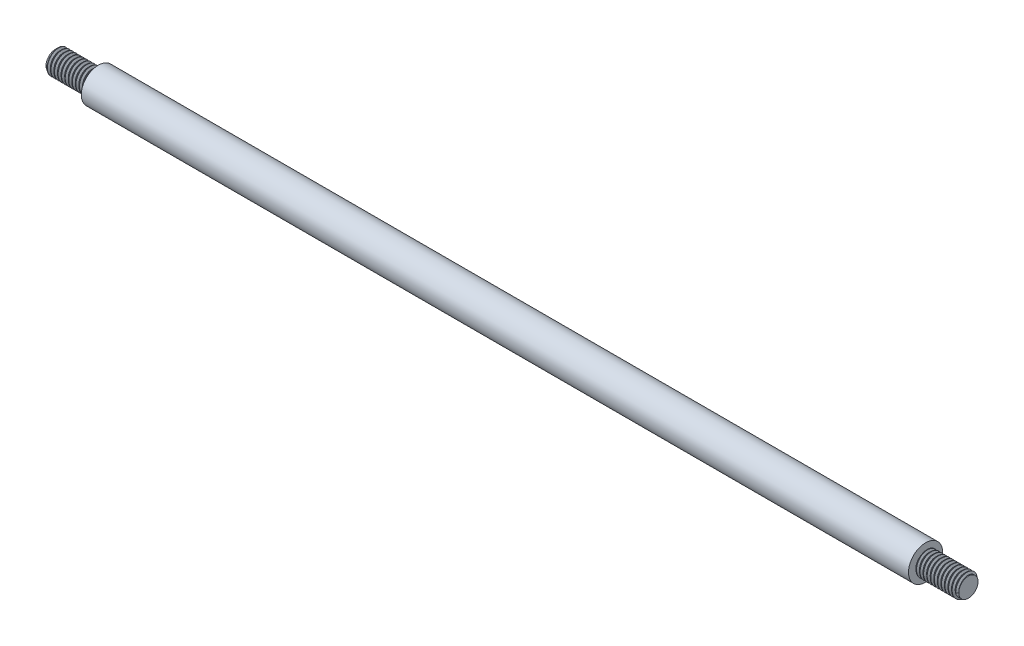
SolidWorks part; units mm, degrees
ref_plane "Спереди" through (0, 0, 0) normal (0, 0, 1) x (1, 0, 0)
ref_plane "Сверху" through (0, 0, 0) normal (0, 1, 0) x (1, 0, 0)
ref_plane "Справа" through (0, 0, 0) normal (1, 0, 0) x (0, 0, -1)
sketch "Эскиз1" plane through (0, 0, 0) normal (0, 0, 1) x (1, 0, 0)
  line L0 (0, -280.2659) -> (0, 13733.0269) construction
  line L1 (-280.2659, 0) -> (13733.0269, 0) construction
  line L2 (-145, 6) -> (145, 6)
  line L3 (145, 6) -> (145, 3.375)
  line L4 (145, 3.375) -> (160, 3.375)
  line L5 (160, 3.375) -> (160, 0)
  line L6 (-160, 3.375) -> (-160, 0)
  line L7 (-145, 3.375) -> (-160, 3.375)
  line L8 (-145, 6) -> (-145, 3.375)
  line L9 (160, 0) -> (-160, 0)
  point P14 (0, 6)
  dimension "D1" = 6.75
  dimension "D2" = 15
  dimension "D3" = 12
  dimension "D4" = 320
revolve "Повернуть1" add sketch "Эскиз1" angle 360 about L9
thread "Резьба1" pitch 1.25 start angle 0, offset 0, length 0, pitch 1.25, diameter 6.75
ref_plane "Плоскость1" through (-160, 0, -3.375) normal (0, -1, 0) x (0, 0, -1)
sketch "Профиль резьбы1" plane through (-160, 0, -3.375) normal (0, -1, 0) x (0, 0, -1)
  line L0 (0, 0) -> (0, 1.25) construction
  line L1 (0, 0) -> (0.6766, 0.3906)
  line L2 (0.6766, 0.3906) -> (0.6766, 0.5469)
  line L3 (0.6766, 0.5469) -> (0, 0.9375)
  line L4 (0.6766, 0.4687) -> (0, 0.4687) construction
  line L11 (0, 0) -> (0, 0.9375)
  point P2 (0, 0)
  dimension "Pitch" = 1.25
  dimension "Profile_Angle" = 60
  dimension "Profile_Land" = 0.1562
  dimension "Profile_Height" = 0.6766
thread "Резьба2" pitch 1.25 profile "Профиль резьбы2" start angle 0, offset 0, length 0, pitch 1.25, diameter 6.75
ref_plane "Плоскость2" through (160, 0, 3.375) normal (0, -1, 0) x (0, 0, 1)
sketch "Профиль резьбы2" plane through (160, 0, 3.375) normal (0, -1, 0) x (0, 0, 1)
  line L0 (0, 0) -> (0, 1.25) construction
  line L1 (0, 0) -> (0.6766, 0.3906)
  line L2 (0.6766, 0.3906) -> (0.6766, 0.5469)
  line L3 (0.6766, 0.5469) -> (0, 0.9375)
  line L4 (0.6766, 0.4687) -> (0, 0.4687) construction
  line L11 (0, 0) -> (0, 0.9375)
  point P2 (0, 0)
  dimension "Pitch" = 1.25
  dimension "Profile_Angle" = 60
  dimension "Profile_Land" = 0.1562
  dimension "Profile_Height" = 0.6766
